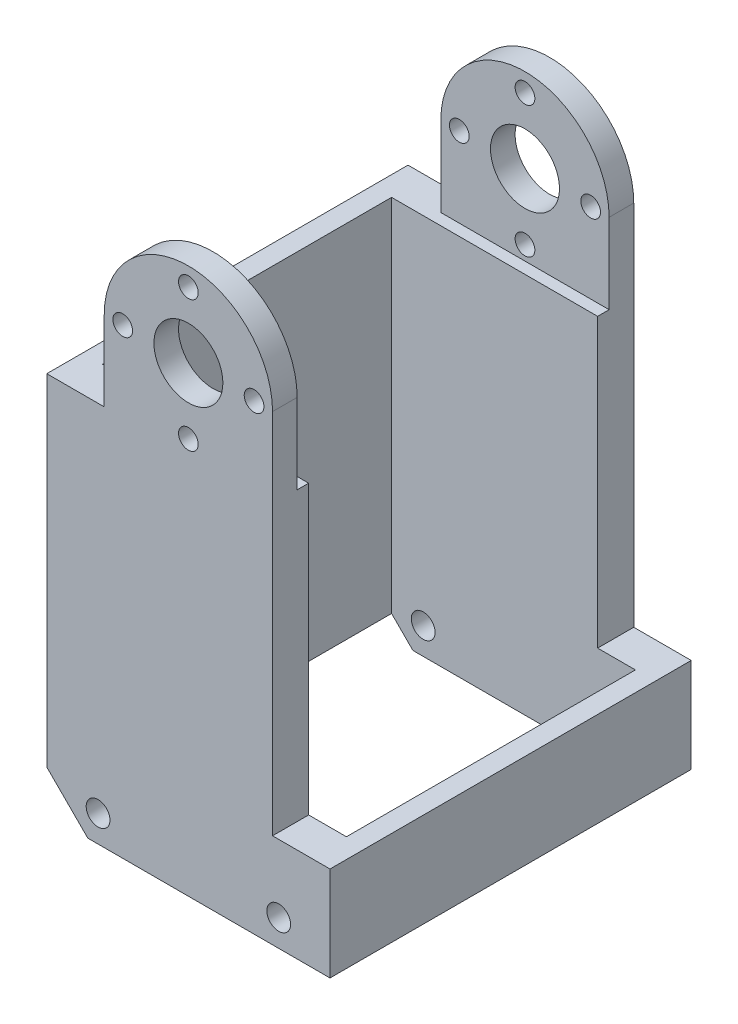
SolidWorks part; units mm, degrees
ref_plane "Front Plane" through (0, 0, 0) normal (0, 0, 1) x (1, 0, 0)
ref_plane "Top Plane" through (0, 0, 0) normal (0, 1, 0) x (1, 0, 0)
ref_plane "Right Plane" through (0, 0, 0) normal (1, 0, 0) x (0, 0, -1)
sketch "Sketch1" plane through (0, 0, 0) normal (0, 0, 1) x (1, 0, 0)
  line L0 (0, 0) -> (0, -100) construction
  line L1 (0, -100) -> (-70, -100) construction
  line L2 (-10.25, -60) -> (-70, -60) construction
  line L4 (-10.25, 0) -> (10.25, 0)
  line L5 (-10.25, 0) -> (-10.25, -60)
  line L7 (10.25, 0) -> (10.25, -60)
  line L8 (-10.25, 0) -> (10.25, 0)
  line L9 (-10.25, 0) -> (-10.25, -100)
  line L10 (-10.25, -100) -> (10.25, -100)
  line L11 (10.25, 0) -> (10.25, -100)
  circle A0 centre (0, 0) radius 10.25
  circle A1 centre (0, 0) radius 8
  circle A2 centre (0, 0) radius 4.2
  circle A3 centre (0, 8) radius 1.2
  circle A4 centre (8, 0) radius 1.2
  circle A5 centre (0, -8) radius 1.2
  circle A6 centre (-8, 0) radius 1.2
  point P16 (0, 0)
  dimension "D1" = 20.5
  dimension "D2" = 16
  dimension "D3" = 8.4
  dimension "D4" = 2.4
  dimension "D6" = 100
  dimension "D7" = 70
  dimension "D8" = 40
  dimension "D5" = 4
extrude "Boss-Extrude1" add sketch "Sketch1" along normal blind 22 and the other way blind 22 contours A0 L5 L7 | A6 L4 A0 A4 A1 A5 | A6 A1 A5 A4 L4 A2 | A6 L4 A2 A4 A1 A3 | A6 A1 A3 A4 L4 A0 region at (8.972, 1.0478, 0) region at (9.725, -0.2292, 0) region at (6.9906, -0.9364, 0) region at (5.5, 0.1769, 0) region at (0, -53.9967, 0)
sketch "Sketch2" plane through (-10.25, 0, 0) normal (-1, 0, 0) x (0, 0, 1)
  line L0 (22, 10.25) -> (-22, 10.25) construction
  line L1 (-19, 10.25) -> (19, 10.25)
  line L2 (-19, 10.25) -> (-19, -9.75)
  line L3 (-19, -9.75) -> (19, -9.75)
  line L4 (19, 10.25) -> (19, -9.75)
  line L5 (22, 0) -> (22, 10.25) construction
  line L6 (-22, 10.25) -> (-22, 0) construction
  dimension "D1" = 3
  dimension "D2" = 3
  dimension "D3" = 20
extrude "Cut-Extrude1" cut sketch "Sketch2" against normal through all
sketch "Sketch3" plane through (0, -9.75, 0) normal (0, 1, 0) x (1, 0, 0)
  line L1 (-10.25, 22) -> (-17.25, 22)
  line L2 (-10.25, 22) -> (-10.25, -22)
  line L3 (-10.25, -22) -> (-17.25, -22)
  line L4 (-17.25, 22) -> (-17.25, -22)
  line L5 (10.25, 22) -> (17.25, 22)
  line L6 (10.25, 22) -> (10.25, -22)
  line L7 (10.25, -22) -> (17.25, -22)
  line L8 (17.25, 22) -> (17.25, -22)
  dimension "D1" = 7
  dimension "D2" = 7
extrude "Boss-Extrude2" add sketch "Sketch3" against normal blind 65.5
sketch "Sketch23" plane through (0, 0, 22) normal (0, 0, 1) x (1, 0, 0)
  line L0 (10.25, -75.25) -> (17.25, -75.25) construction
  line L4 (10.25, -100) -> (-10.25, -100)
  line L5 (10.25, -100) -> (10.25, -75.25)
  line L6 (10.25, -75.25) -> (-10.25, -75.25)
  line L7 (-10.25, -100) -> (-10.25, -75.25)
  circle A0 centre (0, -85) radius 5
  circle A1 centre (0, 0) radius 4.2 construction
  circle A2 centre (0, -85) radius 8
  circle A3 centre (0, -77) radius 1.2
  circle A5 centre (8, -85) radius 1.2
  circle A6 centre (0, -93) radius 1.2
  circle A7 centre (-8, -85) radius 1.2
  circle A8 centre (0, -85) radius 10.25
  point P20 (0, -85)
  line M11 (-10.25, -100) -> (10.25, -100)
  line M12 (10.25, -100) -> (10.25, -75.25)
  dimension "D1" = 85
  dimension "D2" = 9.75
  dimension "D3" = 2.4
  dimension "D4" = 4
extrude "Cut-Extrude2" cut sketch "Sketch23" against normal through all contours A8 L7 M11 M12 | A2 A7 | A2 A7 | A2 A3 | A2 A3 | A2 A5 | A2 A5 | A2 A6 | A2 A6 | A0 region at (0, -96.1486, 22) region at (0, -85, 22) region at (7.4748, -85, 22) region at (8.4927, -85, 22) region at (0, -77.5252, 22) region at (0, -76.5073, 22) region at (0, -93.4927, 22) region at (0, -92.4748, 22) region at (-7.4748, -85, 22) region at (-8.4927, -85, 22)
sketch "Sketch24" plane through (0, -9.75, 0) normal (0, 1, 0) x (1, 0, 0)
  line L0 (17.25, -22) -> (17.25, 22) construction
  line L1 (-14.25, 17) -> (14.25, 17)
  line L2 (-14.25, 17) -> (-14.25, -17)
  line L3 (-14.25, -17) -> (14.25, -17)
  line L4 (14.25, 17) -> (14.25, -17)
  line L5 (-17.25, 22) -> (-17.25, -22) construction
  line L6 (10.25, 19) -> (-10.25, 19) construction
  line L7 (10.25, -19) -> (-10.25, -19) construction
  dimension "D1" = 3
  dimension "D2" = 3
  dimension "D3" = 2
  dimension "D4" = 2
extrude "Cut-Extrude3" cut sketch "Sketch24" against normal through all
sketch "Sketch26" plane through (0, 0, 22) normal (0, 0, 1) x (1, 0, 0)
  line L0 (-17.25, -75.25) -> (-17.25, -9.75) construction
  line L1 (14.25, -96.25) -> (-14.25, -96.25)
  line L2 (14.25, -96.25) -> (14.25, -49.75)
  line L3 (14.25, -49.75) -> (-14.25, -49.75)
  line L4 (-14.25, -96.25) -> (-14.25, -49.75)
  line L5 (17.25, -75.25) -> (17.25, -9.75) construction
  line L7 (-14.25, -49.75) -> (14.25, -49.75)
  line L8 (-14.25, -49.75) -> (-14.25, -56.5328)
  line L10 (14.25, -49.75) -> (14.25, -56.5328)
  line L11 (-14.25, -49.75) -> (14.25, -49.75)
  line L12 (-14.25, -49.75) -> (-14.25, -56.25)
  line L13 (-14.25, -56.25) -> (14.25, -56.25)
  line L14 (14.25, -49.75) -> (14.25, -56.25)
  line L15 (14.25, -56.25) -> (17.25, -56.25)
  line L16 (14.25, -56.25) -> (14.25, -75.25)
  line L17 (14.25, -75.25) -> (17.25, -75.25)
  line L18 (17.25, -56.25) -> (17.25, -75.25)
  line L19 (-17.25, -75.25) -> (-14.25, -75.25)
  line L20 (-17.25, -75.25) -> (-17.25, -56.25)
  line L21 (-17.25, -56.25) -> (-14.25, -56.25)
  line L22 (-14.25, -75.25) -> (-14.25, -56.25)
  arc A0 (-10.25, -85) -> (10.25, -85) centre (0, -85) ccw construction
  circle A1 centre (-11, -53) radius 1.45
  circle A2 centre (11, -53) radius 1.45
  circle M4 centre (0, -93) radius 1.2
  circle M5 centre (8, -85) radius 1.2
  circle M6 centre (0, -77) radius 1.2
  circle M7 centre (-8, -85) radius 1.2
  circle M8 centre (0, -85) radius 5
  line M14 (-10.25, -75.25) -> (-10.25, -85)
  arc M15 (-10.25, -85) -> (10.25, -85) centre (0, -85) ccw
  line M16 (10.25, -85) -> (10.25, -75.25)
  line M17 (10.25, -75.25) -> (17.25, -75.25)
  line M18 (17.25, -75.25) -> (17.25, -9.75)
  line M24 (-17.25, -9.75) -> (-17.25, -75.25)
  line M25 (-17.25, -75.25) -> (-10.25, -75.25)
  dimension "D4" = 2.9
  dimension "D5" = 3.25
  dimension "D6" = 3.25
  dimension "D1" = 3
  dimension "D2" = 3
  dimension "D3" = 11.25
  dimension "D8" = 3.25
  dimension "D9" = 46.5
  dimension "D7" = 2
extrude "Cut-Extrude6" cut sketch "Sketch26" against normal through all contours L13 L4 L2 M25 M14 M15 M16 M17 M5 M7 M8 M6 M4 | L21 L4 M24 M25 | L15 L2 M17 M18 | A1 | A2 region at (0, -71.8107, 22) region at (15.75, -65.75, 22) region at (-15.75, -65.75, 22) region at (-11, -53, 22) region at (11, -53, 22)
sketch "Sketch27" plane through (0, -56.25, 0) normal (0, -1, 0) x (1, 0, 0)
  line L0 (-14.25, 17) -> (14.25, 17) construction
  line L1 (-14.85, -17.6) -> (14.85, -17.6)
  line L2 (-14.85, -17.6) -> (-14.85, 17.6)
  line L3 (-14.85, 17.6) -> (14.85, 17.6)
  line L4 (14.85, -17.6) -> (14.85, 17.6)
  line L5 (-14.85, -17.6) -> (14.85, 17.6) construction
  line L6 (-14.85, 17.6) -> (14.85, -17.6) construction
  line L7 (14.25, 17) -> (14.25, -17) construction
  point P0 (0, 0)
  dimension "D1" = 0.6
  dimension "D2" = 0.6
extrude "Cut-Extrude8" cut sketch "Sketch27" against normal through all
sketch "Sketch29" plane through (0, 0, -22) normal (0, 0, -1) x (-1, 0, 0)
  line L1 (-17.25, -9.75) -> (-10.25, -9.75)
  line L2 (-17.25, -9.75) -> (-17.25, -44.75)
  line L3 (-17.25, -44.75) -> (-10.25, -44.75)
  line L4 (-10.25, -9.75) -> (-10.25, -44.75)
  dimension "D1" = 35
extrude "Cut-Extrude10" cut sketch "Sketch29" against normal through all
chamfer "Chamfer2" distance 5 angle 45 1 edges at (-17.25, -56.25, 0)
